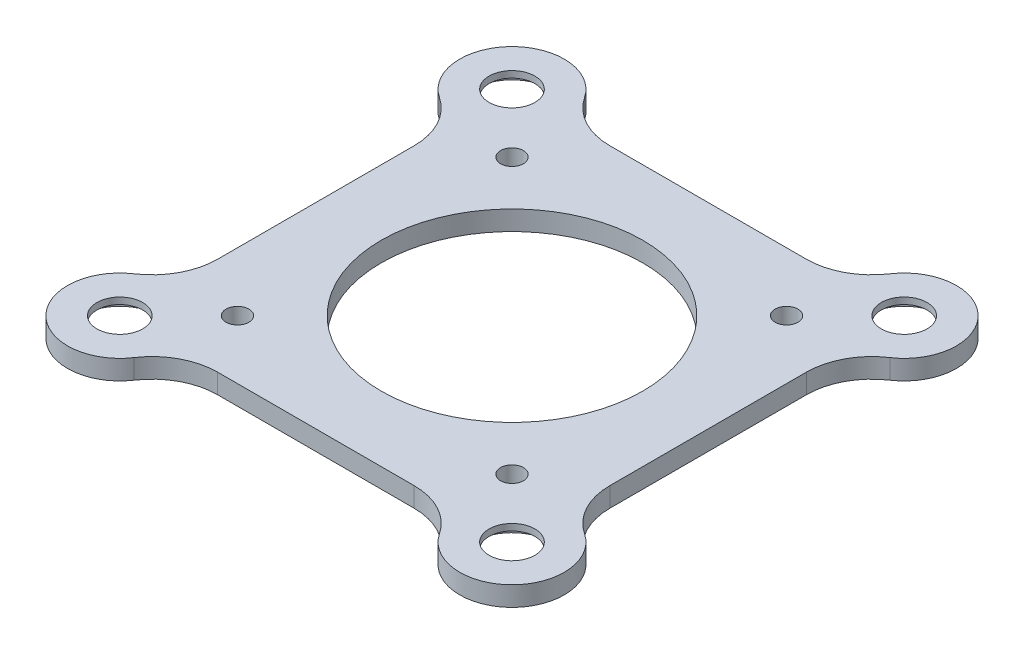
SolidWorks part; units mm, degrees
ref_plane "Спереди" through (0, 0, 0) normal (0, 0, 1) x (1, 0, 0)
ref_plane "Сверху" through (0, 0, 0) normal (0, 1, 0) x (1, 0, 0)
ref_plane "Справа" through (0, 0, 0) normal (1, 0, 0) x (0, 0, -1)
sketch "Эскиз1" plane through (0, 0, 0) normal (0, 1, 0) x (1, 0, 0)
  line L0 (0, 30) -> (60, 30) construction
  line L1 (0, 0) -> (60, 0)
  line L2 (0, 0) -> (0, 60)
  line L3 (0, 60) -> (60, 60)
  line L4 (60, 0) -> (60, 60)
  line L6 (9, 9) -> (51, 9)
  line L7 (9, 9) -> (9, 51)
  line L8 (9, 51) -> (51, 51)
  line L9 (51, 9) -> (51, 51)
  line L10 (9, 9) -> (51, 51) construction
  line L11 (9, 51) -> (51, 9) construction
  circle A0 centre (60, 60) radius 8
  circle A1 centre (0, 60) radius 8
  circle A2 centre (60, 0) radius 8
  circle A3 centre (0, 0) radius 8
  circle A5 centre (30, 30) radius 20
  circle A6 centre (9, 51) radius 1.75
  circle A7 centre (51, 51) radius 1.75
  circle A8 centre (51, 9) radius 1.75
  circle A9 centre (9, 9) radius 1.75
  dimension "D3" = 16
  dimension "D4" = 40
  dimension "D5" = 42
  dimension "D6" = 3.5
  dimension "D1" = 60
  dimension "D2" = 60
extrude "Бобышка-Вытянуть1" add sketch "Эскиз1" along normal blind 3 contours A9 L6 A8 L9 A7 L8 A6 L7 A5 | A3 L1 A2 L4 A0 L3 A1 L2 A9 L7 A6 L8 A7 L9 A8 L6 | L2 A1 L3 | L3 A1 L2 | L3 A0 L4 | L4 A0 L3 | L4 A2 L1 | L1 A2 L4 | L1 A3 L2 | L2 A3 L1 region at (3.3953, 0, -3.3953) region at (-1.1318, 0, 1.1318) region at (6.2569, 0, -6.2569) region at (56.6047, 0, -3.3953) region at (61.1318, 0, 1.1318) region at (-1.1318, 0, -61.1318) region at (3.3953, 0, -56.6047) region at (56.6047, 0, -56.6047) region at (61.1318, 0, -61.1318) region at (10.6574, 0, -10.6574)
fillet "Скругление1" radius 10 8 edges at (52, 1.5, -60) (8, 1.5, -60) (0, 1.5, -52) (0, 1.5, -8) (8, 1.5, 0) (52, 1.5, 0) (60, 1.5, -8) (60, 1.5, -52)
sketch "Эскиз2" plane through (0, 3, 0) normal (0, 1, 0) x (1, 0, 0)
  circle A0 centre (0, 60) radius 6
  circle A1 centre (60, 60) radius 6
  circle A2 centre (60, 0) radius 6
  circle A3 centre (0, 0) radius 6
  circle A4 centre (0, 0) radius 3.5
  circle A5 centre (0, 60) radius 3.5
  circle A6 centre (60, 60) radius 3.5
  circle A7 centre (60, 0) radius 3.5
  dimension "D1" = 12
  dimension "D2" = 7
extrude "Вырез-Вытянуть1" cut sketch "Эскиз2" along normal blind 2 from surface contours A3 | A0 | A1 | A2 starting at face at (30, 0, -30)
extrude "Вырез-Вытянуть3" cut sketch "Эскиз2<3>" against normal through all contours A4 | A5 | A6 | A7 region at (0, 3, 0) region at (0, 3, -60) region at (60, 3, -60) region at (60, 3, 0)
sketch "Эскиз2<3>" plane through (0, 3, 0) normal (0, 1, 0) x (1, 0, 0) same geometry as "Эскиз2"
sketch "Эскиз3" plane through (0, 3, 0) normal (0, 1, 0) x (1, 0, 0)
  line L0 (11.1213, 53.1213) -> (6.8787, 48.8787) construction
  line L1 (14.6569, 49.5858) -> (10.4142, 45.3431)
  line L2 (7.5858, 56.6569) -> (3.3431, 52.4142)
  line L3 (0, 30) -> (60, 30) construction
  line L4 (0, 14.9666) -> (0, 45.0334) construction
  line L5 (60, 14.9666) -> (60, 45.0334) construction
  line L6 (30, 60) -> (30, 0) construction
  line L7 (14.9666, 60) -> (45.0334, 60) construction
  line L8 (14.9666, 0) -> (45.0334, 0) construction
  line L9 (14.0865, 57.1472) -> (9.5877, 52.6484)
  line L10 (15.1472, 56.0865) -> (10.6484, 51.5877)
  line L11 (14.0865, 57.1472) -> (15.1472, 56.0865) construction
  line L12 (5.9948, 55.0659) -> (13.0659, 47.9948)
  line L13 (9.5303, 51.5303) -> (8.4697, 50.4697)
  line L14 (12.0052, 46.9341) -> (4.9341, 54.0052)
  line L15 (5.4645, 54.5355) -> (12.5355, 47.4645) construction
  line L16 (3.9135, 44.8528) -> (8.4123, 49.3516)
  line L17 (2.8528, 45.9135) -> (7.3516, 50.4123)
  line L18 (48.8787, 53.1213) -> (53.1213, 48.8787) construction
  line L19 (45.3431, 49.5858) -> (49.5858, 45.3431)
  line L20 (52.4142, 56.6569) -> (56.6569, 52.4142)
  line L21 (54.5355, 54.5355) -> (47.4645, 47.4645) construction
  line L22 (45.9135, 57.1472) -> (44.8528, 56.0865) construction
  line L23 (57.1472, 45.9135) -> (52.6484, 50.4123)
  line L24 (56.0865, 44.8528) -> (51.5877, 49.3516)
  line L25 (47.9948, 46.9341) -> (55.0659, 54.0052)
  line L26 (50.4697, 51.5303) -> (51.5303, 50.4697)
  line L27 (54.0052, 55.0659) -> (46.9341, 47.9948)
  line L28 (44.8528, 56.0865) -> (49.3516, 51.5877)
  line L29 (45.9135, 57.1472) -> (50.4123, 52.6484)
  line L30 (11.1213, 6.8787) -> (6.8787, 11.1213) construction
  line L31 (14.6569, 10.4142) -> (10.4142, 14.6569)
  line L32 (7.5858, 3.3431) -> (3.3431, 7.5858)
  line L33 (48.8787, 6.8787) -> (53.1213, 11.1213) construction
  line L34 (45.3431, 10.4142) -> (49.5858, 14.6569)
  line L35 (52.4142, 3.3431) -> (56.6569, 7.5858)
  line L36 (45.9135, 2.8528) -> (44.8528, 3.9135) construction
  line L37 (54.5355, 5.4645) -> (47.4645, 12.5355) construction
  line L38 (5.4645, 5.4645) -> (12.5355, 12.5355) construction
  line L39 (14.0865, 2.8528) -> (15.1472, 3.9135) construction
  line L40 (45.9135, 2.8528) -> (50.4123, 7.3516)
  line L41 (44.8528, 3.9135) -> (49.3516, 8.4123)
  line L42 (54.0052, 4.9341) -> (46.9341, 12.0052)
  line L43 (50.4697, 8.4697) -> (51.5303, 9.5303)
  line L44 (47.9948, 13.0659) -> (55.0659, 5.9948)
  line L45 (56.0865, 15.1472) -> (51.5877, 10.6484)
  line L46 (57.1472, 14.0865) -> (52.6484, 9.5877)
  line L47 (2.8528, 14.0865) -> (7.3516, 9.5877)
  line L48 (3.9135, 15.1472) -> (8.4123, 10.6484)
  line L49 (12.0052, 13.0659) -> (4.9341, 5.9948)
  line L50 (9.5303, 8.4697) -> (8.4697, 9.5303)
  line L51 (5.9948, 4.9341) -> (13.0659, 12.0052)
  line L52 (15.1472, 3.9135) -> (10.6484, 8.4123)
  line L53 (14.0865, 2.8528) -> (9.5877, 7.3516)
  arc A0 (14.6569, 49.5858) -> (7.5858, 56.6569) centre (11.1213, 53.1213) ccw
  arc A1 (3.3431, 52.4142) -> (10.4142, 45.3431) centre (6.8787, 48.8787) ccw
  circle A2 centre (9, 51) radius 1.75 construction
  circle A3 centre (9, 51) radius 3
  arc A4 (45.3431, 49.5858) -> (52.4142, 56.6569) centre (48.8787, 53.1213) cw
  arc A5 (56.6569, 52.4142) -> (49.5858, 45.3431) centre (53.1213, 48.8787) cw
  circle A6 centre (51, 51) radius 3
  arc A7 (14.6569, 10.4142) -> (7.5858, 3.3431) centre (11.1213, 6.8787) cw
  arc A8 (3.3431, 7.5858) -> (10.4142, 14.6569) centre (6.8787, 11.1213) cw
  arc A9 (45.3431, 10.4142) -> (52.4142, 3.3431) centre (48.8787, 6.8787) ccw
  arc A10 (56.6569, 7.5858) -> (49.5858, 14.6569) centre (53.1213, 11.1213) ccw
  circle A11 centre (51, 9) radius 3
  circle A12 centre (9, 9) radius 3
  point P2 (9, 51)
  point P42 (51, 51)
  point P67 (9, 9)
  point P74 (51, 9)
  circle M30 centre (9, 51) radius 1.75
  dimension "D3" = 5
  dimension "D5" = 6
  dimension "D1" = 45
  dimension "D2" = 6
  dimension "D4" = 1.5
extrude "Вырез-Вытянуть4" [suppressed] cut sketch "Эскиз3" against normal blind 2 contours L9 A0 L2 L12 M30 | L1 A0 L10 L12 M30 | L16 A1 L1 L14 M30 | L2 A1 L17 L14 M30 | L29 A6 L27 L20 A4 | L27 A6 L28 A4 L19 | L25 A6 L23 A5 L20 | L24 A6 L25 L19 A5 | L48 A12 L49 L31 A8 | L49 A12 L47 A8 L32 | L53 A12 L51 L32 A7 | L51 A12 L52 A7 L31 | A11 L42 L34 A9 L41 | A11 L40 A9 L35 L42 | A11 L45 A10 L34 L44 | A11 L44 L35 A10 L46
sketch "Эскиз4" plane through (0, 3, 0) normal (0, 1, 0) x (1, 0, 0)
  circle A0 centre (0, 60) radius 6
  circle A1 centre (60, 60) radius 6
  circle A2 centre (60, 0) radius 6
  circle A3 centre (0, 0) radius 6
  dimension "D1" = 12
extrude "Вырез-Вытянуть5" [suppressed] cut sketch "Эскиз4" against normal blind 2
sketch "Эскиз5" plane through (0, 3, 0) normal (0, 1, 0) x (1, 0, 0)
  line L0 (30, 30) -> (30, 52.5) construction
  line L1 (24.5, 57.5) -> (35.5, 57.5)
  line L2 (22.5, 55.5) -> (22.5, 54.5)
  line L3 (24.5, 52.5) -> (35.5, 52.5)
  line L4 (37.5, 55.5) -> (37.5, 54.5)
  line L5 (14.9666, 60) -> (45.0334, 60) construction
  line L6 (10, 30) -> (50, 30) construction
  line L7 (37.5, 4.5) -> (37.5, 5.5)
  line L8 (24.5, 7.5) -> (35.5, 7.5)
  line L9 (22.5, 4.5) -> (22.5, 5.5)
  line L10 (24.5, 2.5) -> (35.5, 2.5)
  circle A0 centre (30, 30) radius 20 construction
  arc A1 (37.5, 5.5) -> (35.5, 7.5) centre (35.5, 5.5) ccw
  arc A2 (37.5, 4.5) -> (35.5, 2.5) centre (35.5, 4.5) cw
  arc A3 (22.5, 4.5) -> (24.5, 2.5) centre (24.5, 4.5) ccw
  arc A4 (24.5, 7.5) -> (22.5, 5.5) centre (24.5, 5.5) ccw
  arc A5 (35.5, 52.5) -> (37.5, 54.5) centre (35.5, 54.5) ccw
  arc A6 (35.5, 57.5) -> (37.5, 55.5) centre (35.5, 55.5) cw
  arc A7 (22.5, 54.5) -> (24.5, 52.5) centre (24.5, 54.5) ccw
  arc A8 (24.5, 57.5) -> (22.5, 55.5) centre (24.5, 55.5) ccw
  point P19 (37.5, 7.5)
  point P22 (37.5, 2.5)
  point P25 (22.5, 2.5)
  point P28 (22.5, 7.5)
  point P31 (37.5, 52.5)
  point P34 (37.5, 57.5)
  point P37 (22.5, 52.5)
  point P40 (22.5, 57.5)
  dimension "D4" = 2
  dimension "D1" = 15
  dimension "D2" = 5
  dimension "D3" = 2.5
extrude "Вырез-Вытянуть6" cut sketch "Эскиз5" along normal blind 1.5 from surface starting at face at (60, 0, 6)
chamfer "Фаска1" [suppressed] distance 2 angle 45
